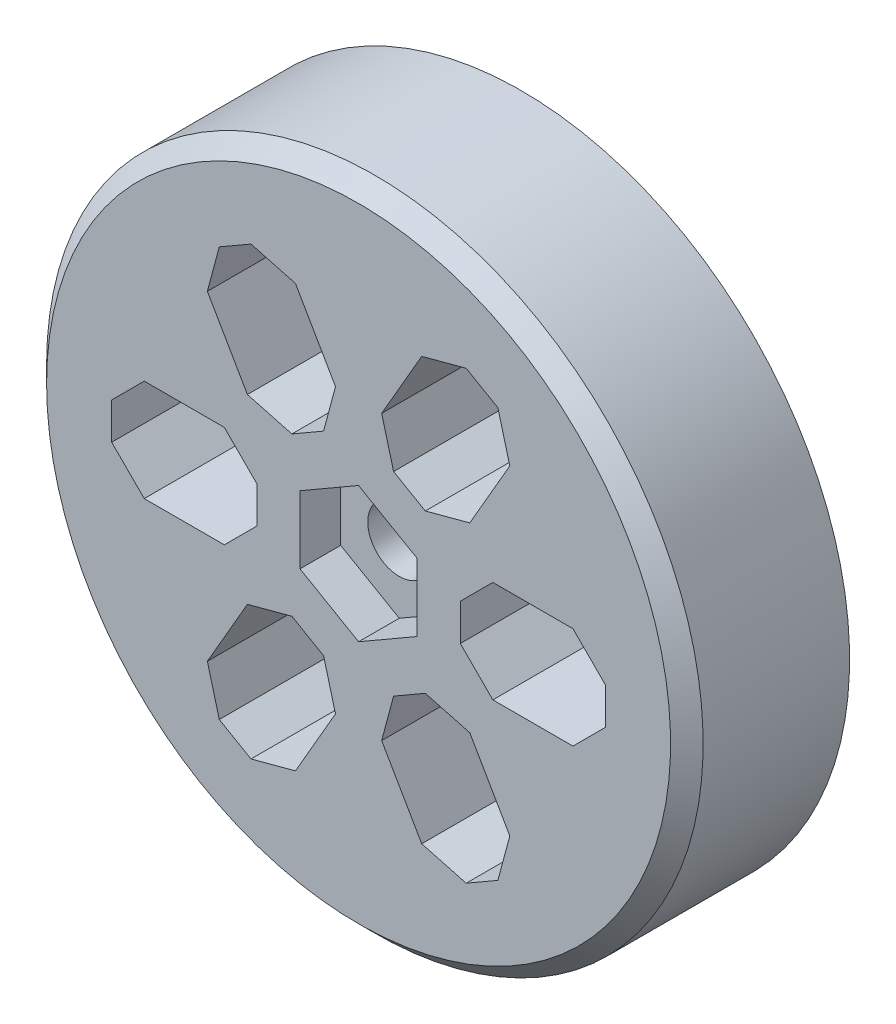
SolidWorks part; units mm, degrees
material "PET"
ref_plane "Front Plane" through (0, 0, 0) normal (0, 0, 1) x (1, 0, 0)
ref_plane "Top Plane" through (0, 0, 0) normal (0, 1, 0) x (1, 0, 0)
ref_plane "Right Plane" through (0, 0, 0) normal (1, 0, 0) x (0, 0, -1)
sketch "Sketch1" plane through (0, 0, 0) normal (0, 0, 1) x (1, 0, 0)
  circle A0 centre (0, 0) radius 25.6159
  dimension "D1" = 51.2318
extrude "Boss-Extrude1" add sketch "Sketch1" along normal blind 12.7
chamfer "Chamfer1" distance 1.27 angle 45 1 edges at (25.6159, 0, 12.7)
sketch "Sketch2" plane through (0, 0, 12.7) normal (0, 0, 1) x (1, 0, 0)
  line L0 (0, -55) -> (0, 55) construction
  line L1 (-4.572, -2.6396) -> (0, -5.2793)
  line L2 (0, -5.2793) -> (4.572, -2.6396)
  line L3 (4.572, -2.6396) -> (4.572, 2.6396)
  line L4 (4.572, 2.6396) -> (0, 5.2793)
  line L5 (0, 5.2793) -> (-4.572, 2.6396)
  line L6 (-4.572, 2.6396) -> (-4.572, -2.6396)
  circle A0 centre (0, 0) radius 4.572 construction
  circle A1 centre (0, 0) radius 25.6159 construction
  dimension "D1" = 9.144
extrude "Cut-Extrude1" cut sketch "Sketch2" against normal blind 3.175
hole_wizard "#8 Clearance Hole1" positions "Sketch3" profile "Sketch4" hole size "#8" standard "ANSI Inch" end condition through all
sketch "Sketch3" plane through (0, 0, 12.7) normal (0, 0, 1) x (1, 0, 0)
  point P0 (0, 0)
sketch "Sketch4" plane through (0, 0, 12.7) normal (1, 0, 0) x (0, -1, 0)
  line L0 (0, 0) -> (0, 12.7)
  line L1 (0, 12.7) -> (2.4574, 12.7)
  line L2 (2.4574, 12.7) -> (2.4574, 0)
  line L5 (2.4574, 0) -> (0, 0)
  line L11 (0, -6.35) -> (0, 107.95) construction
  dimension "Thru Hole Dia." = 4.9149
  dimension "Thru Hole Depth" = 12.7
sketch "Sketch5" plane through (0, 0, 12.7) normal (0, 0, 1) x (1, 0, 0)
  line L0 (-2.286, -3.9595) -> (-3.9687, -6.8741) construction
  line L1 (-4.572, -2.6396) -> (0, -5.2793) construction
  line L2 (-3.9687, -6.8741) -> (-9.6329, -16.6848)
  line L3 (-4.572, 0) -> (-7.9375, 0) construction
  line L4 (-4.572, 2.6396) -> (-4.572, -2.6396) construction
  line L5 (-7.9375, 0) -> (-19.2659, 0)
  line L6 (-2.286, 3.9595) -> (-3.9687, 6.8741) construction
  line L7 (0, 5.2793) -> (-4.572, 2.6396) construction
  line L8 (-3.9687, 6.8741) -> (-9.6329, 16.6848)
  line L9 (2.286, 3.9595) -> (3.9687, 6.8741) construction
  line L10 (4.572, 2.6396) -> (0, 5.2793) construction
  line L11 (3.9687, 6.8741) -> (9.6329, 16.6848)
  line L12 (4.572, 0) -> (7.9375, 0) construction
  line L13 (4.572, -2.6396) -> (4.572, 2.6396) construction
  line L14 (7.9375, 0) -> (19.2659, 0)
  line L15 (2.286, -3.9595) -> (3.9688, -6.8741) construction
  line L16 (0, -5.2793) -> (4.572, -2.6396) construction
  line L17 (3.9688, -6.8741) -> (9.633, -16.6848)
  circle A0 centre (0, 0) radius 19.2659 construction
  circle A1 centre (0, 0) radius 7.9375 construction
  circle A2 centre (0, 0) radius 25.6159 construction
  dimension "D1" = 6.35
  dimension "D2" = 15.875
extrude "Cut-Extrude-Thin1" cut sketch "Sketch5" against normal through all thin thin type mid plane wall 7.9375
chamfer "Chamfer2" distance 2.54 angle 45 24 edges at (-13.07, -14.7004, 6.35) (-6.1959, -18.6691, 6.35) (-7.4058, -4.8897, 6.35) (-0.5317, -8.8585, 6.35) (0.5317, -8.8585, 6.35) (6.1959, -18.6691, 6.35) (13.07, -14.7004, 6.35) (7.4058, -4.8897, 6.35) (19.2659, 3.9688, 6.35) (19.2659, -3.9688, 6.35) (7.9375, -3.9688, 6.35) (7.9375, 3.9688, 6.35) (6.1959, 18.6691, 6.35) (0.5317, 8.8585, 6.35) (7.4058, 4.8897, 6.35) (13.07, 14.7004, 6.35) (-13.07, 14.7004, 6.35) (-7.4058, 4.8897, 6.35) (-0.5317, 8.8585, 6.35) (-6.1959, 18.6691, 6.35) (-19.2659, 3.9688, 6.35) (-19.2659, -3.9688, 6.35) (-7.9375, -3.9688, 6.35) (-7.9375, 3.9688, 6.35)
